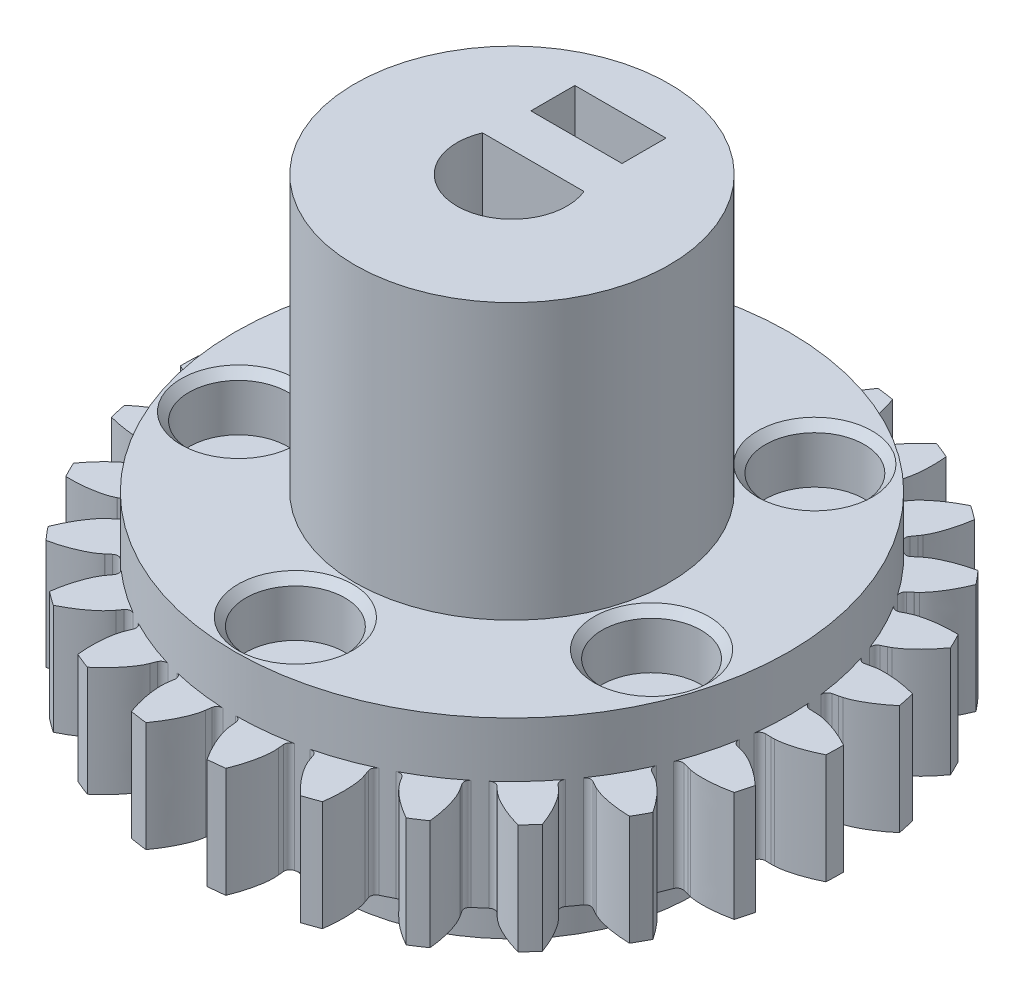
SolidWorks part; units mm, degrees
ref_plane "Front Plane" through (0, 0, 0) normal (0, 0, 1) x (1, 0, 0)
ref_plane "Top Plane" through (0, 0, 0) normal (0, 1, 0) x (1, 0, 0)
ref_plane "Right Plane" through (0, 0, 0) normal (1, 0, 0) x (0, 0, -1)
sketch "Sketch1" plane through (0, 0, 0) normal (0, 1, 0) x (1, 0, 0)
  line L0 (0, 18.325) -> (0, 0) construction
  line L1 (0, 0) -> (18.325, 0) construction
  line L2 (0, 0) -> (18.0994, 2.8667) construction
  line L3 (0, 0) -> (17.4281, 5.6627) construction
  line L4 (0, 0) -> (16.3277, 8.3194) construction
  line L5 (0, 0) -> (14.8252, 10.7712) construction
  line L6 (0, 0) -> (12.9577, 12.9577) construction
  line L7 (0, 0) -> (10.7712, 14.8252) construction
  line L8 (0, 0) -> (8.3194, 16.3277) construction
  line L9 (0, 0) -> (5.6627, 17.4281) construction
  line L10 (0, 0) -> (2.8667, 18.0994) construction
  line L11 (0, 0) -> (0, 18.325) construction
  line L12 (12.9577, 12.9577) -> (14.9942, 10.9213)
  line L13 (10.7712, 14.8252) -> (15.4311, 11.4396)
  line L14 (8.3194, 16.3277) -> (16.0177, 12.4052)
  line L15 (5.6627, 17.4281) -> (16.6189, 13.8682)
  line L16 (15.6524, 9.5293) -> (0, 0) construction
  line L17 (2.8667, 18.0994) -> (33.1393, 13.3047)
  line L18 (14.8696, 12.6152) -> (0, 0) construction
  line L19 (14.8252, 10.7712) -> (13.0429, 12.872)
  line L20 (14.8252, 10.7712) -> (14.2899, 10.317)
  line L21 (13.0429, 12.872) -> (12.5076, 12.4178)
  circle A0 centre (0, 0) radius 18.325
  circle A1 centre (0, 0) radius 21
  circle A2 centre (0, 0) radius 17.625
  circle A3 centre (0, 0) radius 19.5 construction
  spline S0 degree 2 poles (14.8252, 10.7712) (15.1748, 11.06) (15.4311, 11.4396) knots 0 0 0 1 1 1
  spline S1 degree 3 poles (14.8252, 10.7712) (15.0602, 10.961) (15.8365, 11.8956) (16.3364, 13.0109) (16.6189, 13.8682) knots 0 0 0 0 0.250011 1 1 1 1
  spline S2 degree 3 poles (13.0429, 12.872) (13.2685, 13.0729) (14.3171, 13.6865) (15.499, 13.998) (16.3909, 14.137) knots 0 0 0 0 0.250011 1 1 1 1
  point P4 (15.6524, 9.5293)
  point P6 (16.0604, 11.0595)
  point P10 (15.6053, 11.6929)
  point P18 (0, 0)
  point P25 (14.8696, 12.6152)
  dimension "D10" = 30.65
  dimension "D11" = 39
  dimension "D9" = 36.65
  dimension "D3" = 35.25
  dimension "D19" = 42
  dimension "D2" = 9
  dimension "D4" = 2.88
  dimension "D5" = 9
  dimension "D6" = 5.76
  dimension "D7" = 8.64
  dimension "D8" = 11.52
  dimension "D12" = 9
  dimension "D13" = 9
  dimension "D14" = 9
  dimension "D15" = 9
  dimension "D16" = 9
  dimension "D17" = 9
  dimension "D18" = 9
  dimension "D20" = 1.96
  dimension "D21" = 1.18
extrude "Boss-Extrude2" add sketch "Sketch1" along normal blind 7
sketch "Sketch2" plane through (0, 0, 0) normal (0, 0, 1) x (1, 0, 0)
  line L2 (0, -16.8661) -> (0, 28.4013) construction
pattern_circular "CirPattern1" count 26 over 360 about axis through (0, -16.8661, 0) along (0, 1, 0) of "Boss-Extrude2"
fillet "Fillet2" radius 0.375 104 edges at (11.8167, 3.5, -14.0061) (11.4056, 3.5, -13.437) (9.1724, 3.5, -15.0502) (9.5835, 3.5, -15.6193) (8.1215, 3.5, -16.427) (7.8585, 3.5, -15.7761) (5.3041, 3.5, -16.8079) (5.5671, 3.5, -17.4589) (3.9542, 3.5, -17.8933) (3.8547, 3.5, -17.1983) (1.1276, 3.5, -17.5889) (1.2271, 3.5, -18.2839) (-0.4428, 3.5, -18.3196) (-0.3731, 3.5, -17.621) (-3.1145, 3.5, -17.3476) (-3.1842, 3.5, -18.0462) (-4.8141, 3.5, -17.6813) (-4.5793, 3.5, -17.0197) (-7.1756, 3.5, -16.0982) (-7.4104, 3.5, -16.7598) (-8.9056, 3.5, -16.0155) (-8.5193, 3.5, -15.4293) (-10.8196, 3.5, -13.9132) (-11.2059, 3.5, -14.4994) (-12.4796, 3.5, -13.4188) (-11.9642, 3.5, -12.9421) (-13.8348, 3.5, -10.9196) (-14.3503, 3.5, -11.3963) (-15.3283, 3.5, -10.0423) (-14.7138, 3.5, -9.7028) (-16.0461, 3.5, -7.2914) (-16.6606, 3.5, -7.6309) (-17.2862, 3.5, -6.0822) (-16.6083, 3.5, -5.8996) (-17.3247, 3.5, -3.2395) (-18.0026, 3.5, -3.422) (-18.2395, 3.5, -1.7686) (-17.5375, 3.5, -1.7536) (-17.5966, 3.5, 1.0008) (-18.2985, 3.5, 0.9857) (-18.1327, 3.5, 2.6478) (-17.4476, 3.5, 2.4944) (-16.8457, 3.5, 5.1828) (-17.5309, 3.5, 5.3362) (-16.9722, 3.5, 6.9103) (-16.3437, 3.5, 6.5974) (-15.1159, 3.5, 9.0637) (-15.7444, 3.5, 9.3765) (-14.8252, 3.5, 10.7712) (-14.2899, 3.5, 10.317) (-12.5076, 3.5, 12.4178) (-13.0429, 3.5, 12.872) (-11.8167, 3.5, 14.0061) (-11.4056, 3.5, 13.437) (-9.1724, 3.5, 15.0502) (-9.5835, 3.5, 15.6193) (-8.1215, 3.5, 16.427) (-7.8585, 3.5, 15.7761) (-5.3041, 3.5, 16.8079) (-5.5671, 3.5, 17.4589) (-3.9542, 3.5, 17.8933) (-3.8547, 3.5, 17.1983) (-1.1276, 3.5, 17.5889) (-1.2271, 3.5, 18.2839) (0.4428, 3.5, 18.3196) (0.3731, 3.5, 17.621) (3.1145, 3.5, 17.3476) (3.1842, 3.5, 18.0462) (4.8141, 3.5, 17.6813) (7.1756, 3.5, 16.0982) (7.4104, 3.5, 16.7598) (8.9056, 3.5, 16.0155) (10.8196, 3.5, 13.9132) (11.2059, 3.5, 14.4994) (12.4796, 3.5, 13.4188) (13.8348, 3.5, 10.9196) (14.3503, 3.5, 11.3963) (15.3283, 3.5, 10.0423) (16.0461, 3.5, 7.2914) (16.6606, 3.5, 7.6309) (17.2862, 3.5, 6.0822) (16.6083, 3.5, 5.8996) (17.3247, 3.5, 3.2395) (18.0026, 3.5, 3.422) (18.2395, 3.5, 1.7686) (17.5375, 3.5, 1.7536) (17.5966, 3.5, -1.0008) (18.2985, 3.5, -0.9857) (18.1327, 3.5, -2.6478) (17.4476, 3.5, -2.4944) (16.8457, 3.5, -5.1828) (17.5309, 3.5, -5.3362) (16.9722, 3.5, -6.9103) (16.3437, 3.5, -6.5974) (15.1159, 3.5, -9.0637) (15.7444, 3.5, -9.3765) (14.8252, 3.5, -10.7712) (14.2899, 3.5, -10.317) (12.5076, 3.5, -12.4178) (13.0429, 3.5, -12.872) (14.7138, 3.5, 9.7028) (11.9642, 3.5, 12.9421) (8.5193, 3.5, 15.4293) (4.5793, 3.5, 17.0197)
sketch "Sketch3" plane through (0, 7, 0) normal (0, 1, 0) x (1, 0, 0)
  circle A1 centre (0, 0) radius 10
  dimension "D1" = 20
extrude "Boss-Extrude3" add sketch "Sketch3" along normal blind 21
sketch "Sketch4" plane through (0, 28, 0) normal (0, 1, 0) x (1, 0, 0)
  line L0 (0, 0) -> (0, 3.5) construction
  line L1 (-3.2292, 1.35) -> (3.2292, 1.35)
  line L2 (0, 0) -> (0, -3.5) construction
  circle A0 centre (0, 0) radius 3.5
  dimension "D1" = 7
  dimension "D2" = 4.85
extrude "Cut-Extrude1" cut sketch "Sketch4" against normal blind 10
sketch "Sketch5" plane through (0, 28, 0) normal (0, 1, 0) x (1, 0, 0)
  line L0 (0, 0) -> (0, 10) construction
  circle A2 centre (0, 0) radius 10 construction
ref_plane "Plane1" through (0, 28, -10) normal (0, 0, -1) x (-1, 0, 0)
sketch "Sketch6" plane through (0, 28, -10) normal (0, 0, -1) x (-1, 0, 0)
  line L1 (3.2292, 0) -> (-3.2292, 0) construction
  line L2 (0, -44.8661) -> (0, 0.4013) construction
  circle A0 centre (0, -5) radius 1.6
  dimension "D2" = 3.2
  dimension "D1" = 5
extrude "Cut-Extrude2" cut sketch "Sketch6" against normal blind 15
sketch "Sketch8" plane through (0, 28, 0) normal (0, 1, 0) x (1, 0, 0)
  line L1 (-2.9, 4.1) -> (2.9, 4.1)
  line L2 (-2.9, 4.1) -> (-2.9, 6.9)
  line L3 (-2.9, 6.9) -> (2.9, 6.9)
  line L4 (2.9, 4.1) -> (2.9, 6.9)
  line L5 (0, 0) -> (0, 10) construction
  line L6 (-3.2292, 1.35) -> (3.2292, 1.35) construction
  line L7 (-3.2292, 1.35) -> (3.2292, 1.35) construction
  dimension "D1" = 2.8
  dimension "D2" = 5.8
  dimension "D3" = 2.9
  dimension "D4" = 2.75
  dimension "D5" = 2.75
  dimension "D6" = 3.1
extrude "Cut-Extrude4" cut sketch "Sketch8" against normal blind 8.8
sketch "Sketch9" plane through (0, 0, 0) normal (0, -1, 0) x (1, 0, 0)
  circle A0 centre (0, 0) radius 9.65
  circle A1 centre (0, 0) radius 11.5
  dimension "D1" = 19.3
  dimension "D2" = 23
extrude "Boss-Extrude4" add sketch "Sketch9" along normal blind 6
sketch "Sketch10" plane through (0, 7, 0) normal (0, 1, 0) x (1, 0, 0)
  line L0 (0, 0) -> (0, -10) construction
  line L1 (0, 16.95) -> (0, 17.625) construction
  line L2 (0, -10) -> (0.0333, -17.625) construction
  circle A0 centre (0, 0) radius 17.625
  circle A1 centre (0, 0) radius 10
  circle A7 centre (0.0166, -13.8) radius 3.15
  circle A8 centre (-13.1194, -4.2802) radius 3.15
  circle A9 centre (-8.1249, 11.1547) radius 3.15
  circle A10 centre (8.098, 11.1742) radius 3.15
  circle A11 centre (13.1297, -4.2486) radius 3.15
  dimension "D1" = 3.8
  dimension "D2" = 6.3
  dimension "D3" = 5
extrude "Boss-Extrude5" add sketch "Sketch10" along normal blind 3.5
chamfer "Chamfer1" distance 0.5 angle 45 5 edges at (-13.1194, 10.5, 7.4302) (-8.1249, 10.5, -8.0047) (8.098, 10.5, -8.0242) (13.1297, 10.5, 7.3986) (0.0166, 10.5, 16.95)
equation "\"num_teeth\"= 26"
equation "\"pressure_angle\"= 20"
equation "\"pitch_dia\"= 39"
equation "\"module\"= \"pitch_dia\" / \"num_teeth\""
equation "\"addendum\"= \"module\""
equation "\"dedendum\"= 1.25 * \"module\""
equation "\"base_dia\"= 2 * ( ( \"pitch_dia\" / 2 ) * cos ( \"pressure_angle\" ) )"
equation "\"circular_pitch\"= pi * \"module\""
equation "\"tooth_thickness\"= \"circular_pitch\" / 2"
equation "\"add_circle\"= \"pitch_dia\" + ( 2 * \"addendum\" )"
equation "\"ded_circle\"= \"pitch_dia\" - ( 2 * \"dedendum\" )"
